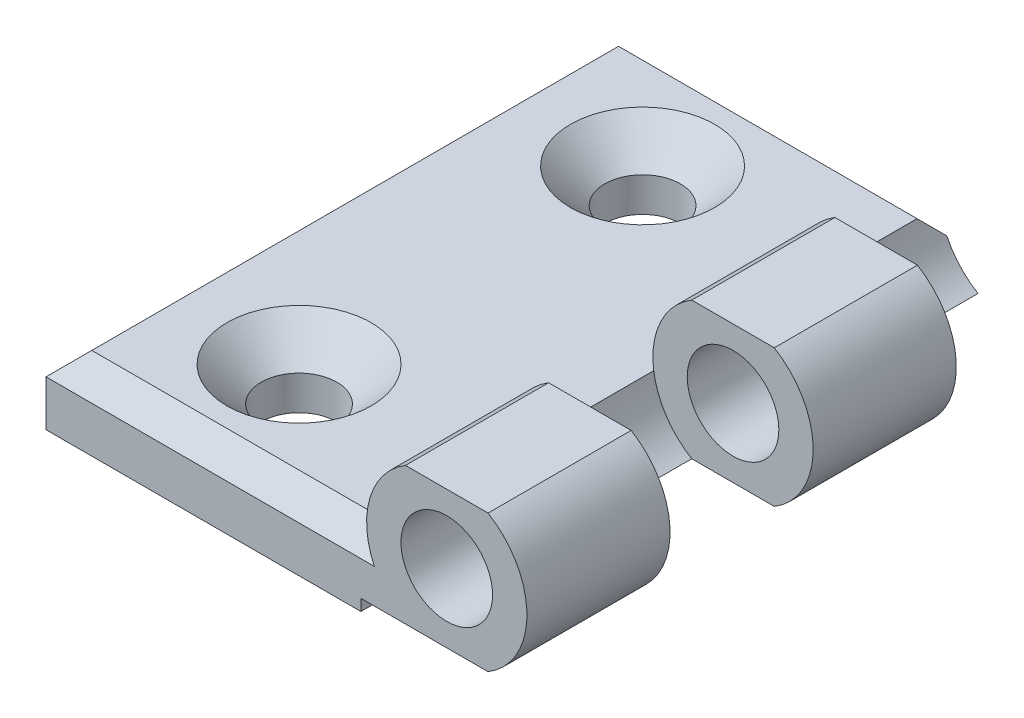
SolidWorks part; units mm, degrees
ref_plane "Ön Düzlem" through (0, 0, 0) normal (0, 0, 1) x (1, 0, 0)
ref_plane "Üst Düzlem" through (0, 0, 0) normal (0, 1, 0) x (1, 0, 0)
ref_plane "Sağ Düzlem" through (0, 0, 0) normal (1, 0, 0) x (0, 0, -1)
sketch "Çizim1" plane through (0, 0, 0) normal (0, 0, 1) x (1, 0, 0)
  line L0 (-7.5, -7) -> (-7.5, -6)
  line L1 (-6.9282, -1) -> (-35, -1)
  line L2 (-7.5, -7) -> (-35, -7)
  line L3 (-7.5, -6) -> (3.6056, -6)
  line L4 (0, 0) -> (0, 7) construction
  line L5 (-35, -7) -> (-35, -1)
  line L6 (3.6056, 6) -> (-3.6056, 6)
  arc A0 (3.6056, -6) -> (3.6056, 6) centre (0, 0) ccw
  circle A1 centre (0, 0) radius 4
  arc A2 (-3.6056, 6) -> (-6.9282, -1) centre (0, 0) ccw
  dimension "D1" = 14
  dimension "D2" = 8
  dimension "D3" = 35
  dimension "D4" = 6
  dimension "D5" = 6.9282
  dimension "D6" = 1
  dimension "D7" = 7.5
  dimension "D9" = 7
  dimension "D10" = 7.2111
extrude "Yükseklik-Ekstrüzyon1" add sketch "Çizim1" along normal mid plane 50
sketch "Çizim2" plane through (0, 6, 0) normal (0, 1, 0) x (1, 0, 0)
  line L0 (0, 25) -> (0, -25) construction
  line L1 (3.6056, 25) -> (-3.6056, 25) construction
  line L2 (3.6056, -25) -> (-3.6056, -25) construction
hole_wizard "M6 Düz Havşa Başlı Vida İçin Havşa1" positions "Çizim3" profile "Çizim4" countersink size "M6" standard "ISO" end condition up to next
sketch "Çizim3" plane through (0, -1, 0) normal (0, 1, 0) x (1, 0, 0)
  line L0 (0, 25) -> (0, -25) construction
  line L1 (-6.9282, -25) -> (-35, -25) construction
  point P0 (-22.9, -15)
  point P7 (-22.9, 15)
  dimension "D1" = 22.9
  dimension "D2" = 10
  dimension "D3" = 30
  dimension "D4" = 22.9
sketch "Çizim4" plane through (-22.9, -1, 15) normal (1, 0, 0) x (0, 0, 1)
  line L0 (0, 0) -> (0, 6)
  line L1 (0, 6) -> (3.3, 6)
  line L2 (3.3, 6) -> (3.3, 3)
  line L3 (3.3, 3) -> (6.3, 0)
  line L5 (6.3, 0) -> (0, 0)
  line L6 (-3.3, 3) -> (-6.3, 0) construction
  line L11 (0, -6.35) -> (0, 107.95) construction
  dimension "Thru Hole Dia." = 6.6
  dimension "Thru Hole Depth" = 6
  dimension "Near C'Sink Dia." = 12.6
  dimension "Near C'Sink Angle" = 90
chamfer "Pah1" distance 2 angle 45 3 edges at (-20.9641, -1, -25) (-35, -1, 0) (-20.9641, -1, 25)
ref_plane "Düzlem1" through (0, 0, 12.5) normal (0, 0, 1) x (1, 0, 0)
sketch "Çizim5" plane through (0, 0, 12.5) normal (0, 0, 1) x (1, 0, 0)
  circle A0 centre (0, 0) radius 7
extrude "Kes-Ekstrüzyon1" cut sketch "Çizim5" against normal blind 12.5
sketch "Çizim7" plane through (0, 0, -25) normal (0, 0, -1) x (-1, 0, 0)
  circle A0 centre (0, 0) radius 7
extrude "Kes-Ekstrüzyon2" cut sketch "Çizim7" against normal blind 12.5
